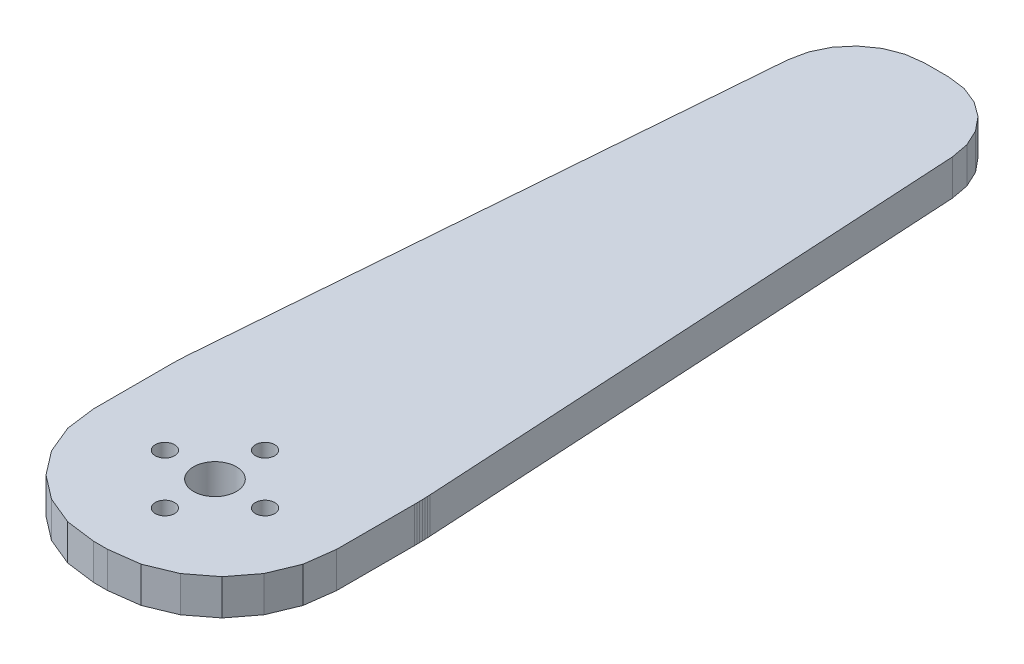
SolidWorks part; units mm, degrees
ref_plane "Front Plane" through (0, 0, 0) normal (0, 0, 1) x (1, 0, 0)
ref_plane "Top Plane" through (0, 0, 0) normal (0, 1, 0) x (1, 0, 0)
ref_plane "Right Plane" through (0, 0, 0) normal (1, 0, 0) x (0, 0, -1)
ref_plane "PY_m5_000" through (0, -5, 0) normal (0, 1, 0) x (1, 0, 0)
sketch "S_prism1" plane through (0, -5, 0) normal (0, 1, 0) x (1, 0, 0)
  line L0 (-17, 0) -> (-16.455, -4.141)
  line L1 (-16.455, -4.141) -> (-14.856, -8)
  line L2 (-14.856, -8) -> (-12.314, -11.314)
  line L3 (-12.314, -11.314) -> (-9, -13.856)
  line L4 (-9, -13.856) -> (-5.141, -15.455)
  line L5 (-5.141, -15.455) -> (-1, -16)
  line L6 (-1, -16) -> (1, -16)
  line L7 (1, -16) -> (5.141, -15.455)
  line L8 (5.141, -15.455) -> (9, -13.856)
  line L9 (9, -13.856) -> (12.314, -11.314)
  line L10 (12.314, -11.314) -> (14.856, -8)
  line L11 (14.856, -8) -> (16.455, -4.141)
  line L12 (16.455, -4.141) -> (17, 0)
  line L13 (17, 0) -> (17, 10.865)
  line L14 (17, 10.865) -> (16.998, 11.243)
  line L15 (16.998, 11.243) -> (16.993, 11.621)
  line L16 (16.993, 11.621) -> (16.984, 12)
  line L17 (16.984, 12) -> (16.971, 12.378)
  line L18 (16.971, 12.378) -> (16.955, 12.756)
  line L19 (16.955, 12.756) -> (16.936, 13.134)
  line L20 (16.936, 13.134) -> (12.536, 90.567)
  line L21 (12.536, 90.567) -> (12.078, 93.042)
  line L22 (12.078, 93.042) -> (11.017, 95.324)
  line L23 (11.017, 95.324) -> (9.42, 97.269)
  line L24 (9.42, 97.269) -> (7.387, 98.753)
  line L25 (7.387, 98.753) -> (5.049, 99.683)
  line L26 (5.049, 99.683) -> (2.552, 100)
  line L27 (2.552, 100) -> (-0.764, 100)
  line L28 (-0.764, 100) -> (-3.224, 99.693)
  line L29 (-3.224, 99.693) -> (-5.533, 98.79)
  line L30 (-5.533, 98.79) -> (-7.549, 97.346)
  line L31 (-7.549, 97.346) -> (-9.148, 95.451)
  line L32 (-9.148, 95.451) -> (-10.231, 93.221)
  line L33 (-10.231, 93.221) -> (-10.732, 90.793)
  line L34 (-10.732, 90.793) -> (-16.874, 13.583)
  line L35 (-16.874, 13.583) -> (-16.913, 13.056)
  line L36 (-16.913, 13.056) -> (-16.944, 12.527)
  line L37 (-16.944, 12.527) -> (-16.968, 11.999)
  line L38 (-16.968, 11.999) -> (-16.986, 11.47)
  line L39 (-16.986, 11.47) -> (-16.996, 10.941)
  line L40 (-16.996, 10.941) -> (-17, 10.412)
  line L41 (-17, 10.412) -> (-17, 0)
  dimension "P1" = 17
  dimension "P2" = 16.455
  dimension "P3" = 4.141
  dimension "P4" = 14.856
  dimension "P5" = 8
  dimension "P6" = 12.314
  dimension "P7" = 11.314
  dimension "P8" = 9
  dimension "P9" = 13.856
  dimension "P10" = 5.141
  dimension "P11" = 15.455
  dimension "P12" = 1
  dimension "P13" = 16
  dimension "P14" = 1
  dimension "P15" = 16
  dimension "P16" = 5.141
  dimension "P17" = 15.455
  dimension "P18" = 9
  dimension "P19" = 13.856
  dimension "P20" = 12.314
  dimension "P21" = 11.314
  dimension "P22" = 14.856
  dimension "P23" = 8
  dimension "P24" = 16.455
  dimension "P25" = 4.141
  dimension "P26" = 17
  dimension "P27" = 17
  dimension "P28" = 10.865
  dimension "P29" = 16.998
  dimension "P30" = 11.243
  dimension "P31" = 16.993
  dimension "P32" = 11.621
  dimension "P33" = 16.984
  dimension "P34" = 12
  dimension "P35" = 16.971
  dimension "P36" = 12.378
  dimension "P37" = 16.955
  dimension "P38" = 12.756
  dimension "P39" = 16.936
  dimension "P40" = 13.134
  dimension "P41" = 12.536
  dimension "P42" = 90.567
  dimension "P43" = 12.078
  dimension "P44" = 93.042
  dimension "P45" = 11.017
  dimension "P46" = 95.324
  dimension "P47" = 9.42
  dimension "P48" = 97.269
  dimension "P49" = 7.387
  dimension "P50" = 98.753
  dimension "P51" = 5.049
  dimension "P52" = 99.683
  dimension "P53" = 2.552
  dimension "P54" = 100
  dimension "P55" = 0.764
  dimension "P56" = 100
  dimension "P57" = 3.224
  dimension "P58" = 99.693
  dimension "P59" = 5.533
  dimension "P60" = 98.79
  dimension "P61" = 7.549
  dimension "P62" = 97.346
  dimension "P63" = 9.148
  dimension "P64" = 95.451
  dimension "P65" = 10.231
  dimension "P66" = 93.221
  dimension "P67" = 10.732
  dimension "P68" = 90.793
  dimension "P69" = 16.874
  dimension "P70" = 13.583
  dimension "P71" = 16.913
  dimension "P72" = 13.056
  dimension "P73" = 16.944
  dimension "P74" = 12.527
  dimension "P75" = 16.968
  dimension "P76" = 11.999
  dimension "P77" = 16.986
  dimension "P78" = 11.47
  dimension "P79" = 16.996
  dimension "P80" = 10.941
  dimension "P81" = 17
  dimension "P82" = 10.412
extrude "Boss_1" add sketch "S_prism1" along normal blind 5
ref_plane "PY_m5_100" through (0, -5.1, 0) normal (0, 1, 0) x (1, 0, 0)
sketch "S_hole2" plane through (0, -5.1, 0) normal (0, 1, 0) x (1, 0, 0)
  circle A0 centre (0, 0) radius 3
  dimension "D1_S_hole2" = 6
extrude "Hole_2" cut sketch "S_hole2" along normal blind 5.2
sketch "S_hole3" plane through (0, -5.1, 0) normal (0, 1, 0) x (1, 0, 0)
  circle A0 centre (7, 0) radius 1.35
  dimension "D1_S_hole3" = 2.7
  dimension "P2" = 7
extrude "Hole_3" cut sketch "S_hole3" along normal blind 5.2
sketch "S_hole4" plane through (0, -5.1, 0) normal (0, 1, 0) x (1, 0, 0)
  circle A0 centre (0, -7) radius 1.35
  dimension "D1_S_hole4" = 2.7
  dimension "P2" = 7
extrude "Hole_4" cut sketch "S_hole4" along normal blind 5.2
sketch "S_hole5" plane through (0, -5.1, 0) normal (0, 1, 0) x (1, 0, 0)
  circle A0 centre (-7, 0) radius 1.35
  dimension "D1_S_hole5" = 2.7
  dimension "P2" = 7
extrude "Hole_5" cut sketch "S_hole5" along normal blind 5.2
sketch "S_hole6" plane through (0, -5.1, 0) normal (0, 1, 0) x (1, 0, 0)
  circle A0 centre (0, 7) radius 1.35
  dimension "D1_S_hole6" = 2.7
  dimension "P2" = 7
extrude "Hole_6" cut sketch "S_hole6" along normal blind 5.2
equation "\"plate_t\" = 3"
equation "\"clearance\" = 0.4"
